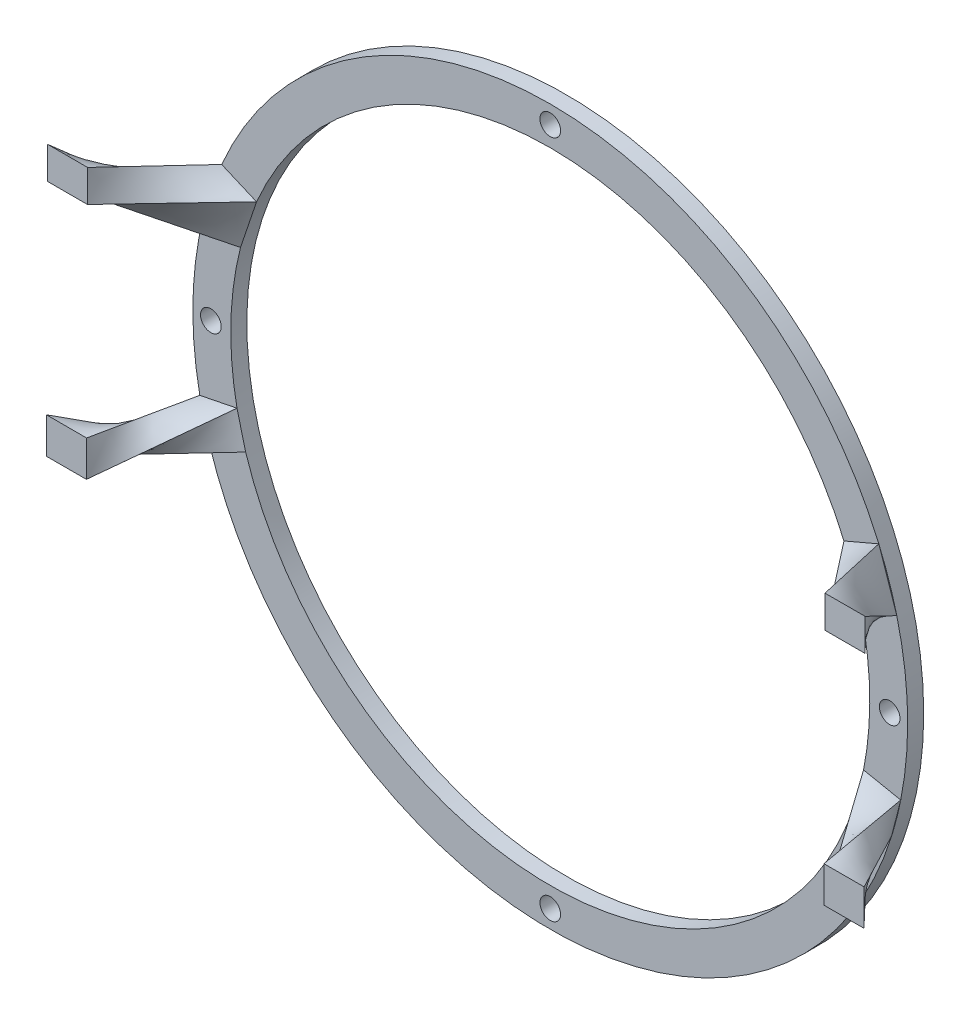
SolidWorks part; units mm, degrees
ref_plane "Front Plane" through (0, 0, 0) normal (0, 0, 1) x (1, 0, 0)
ref_plane "Top Plane" through (0, 0, 0) normal (0, 1, 0) x (1, 0, 0)
ref_plane "Right Plane" through (0, 0, 0) normal (1, 0, 0) x (0, 0, -1)
sketch "Sketch1" plane through (0, 0, 0) normal (0, 0, 1) x (1, 0, 0)
  circle A0 centre (0, 0) radius 89.0365
  circle A1 centre (0, 0) radius 79.5898
  circle A2 centre (0, -84.548) radius 2.5745
  circle A3 centre (-84.548, 0) radius 2.5745
  circle A4 centre (0, 84.548) radius 2.5745
  circle A5 centre (84.548, 0) radius 2.5745
  point P16 (0, 0)
  dimension "D1" = 4
extrude "Boss-Extrude1" add sketch "Sketch1" along normal blind 4
sketch "Sketch2" plane through (0, 0, 4) normal (0, 0, 1) x (1, 0, 0)
  line L2 (86.3259, 21.8023) -> (77.1668, 19.4891)
  line L3 (81.8463, 35.0527) -> (73.1625, 31.3336)
  line L4 (81.8463, 167.6928) -> (81.8463, 27.8766) construction
  line L5 (73.1625, 31.3336) -> (77.1668, 19.4891)
  line L6 (81.8463, 35.0527) -> (86.3259, 21.8023)
  circle A0 centre (0, 0) radius 89.0365 construction
  circle A1 centre (0, 0) radius 79.5898 construction
sketch "Sketch3" plane through (0, 0.1239, 27.5876) normal (0, -0.0045, -1) x (-1, 0, 0)
  line L0 (-101.8463, 40.9901) -> (-101.8463, 33.011)
  line L3 (-91.8463, 40.9901) -> (-91.8463, 33.011)
  line L6 (-101.8463, 40.9901) -> (-91.8463, 40.9901)
  line L7 (-101.8463, -36.3437) -> (-101.8463, 50.7621) construction
  line L8 (-91.8463, -36.3437) -> (-91.8463, 50.7621) construction
  line L9 (-101.8463, 33.011) -> (-91.8463, 33.011)
loft "Loft1" add section "Sketch3" section "Sketch2" connector at (101.8463, 41.1136, 27.4035) connector at (86.3259, 21.8023, 4)
sketch "Sketch8" plane through (0, 0, 4) normal (0, 0, 1) x (1, 0, 0)
  line L3 (78.0403, -15.6285) -> (87.3031, -17.4835)
  line L4 (87.3031, -17.4835) -> (85.0502, -26.3434)
  line L5 (85.0502, -26.3434) -> (75.8813, -24.0119)
  line L6 (75.8813, -24.0119) -> (78.0403, -15.6285)
  arc A3 (73.1625, 31.3336) -> (77.1668, 19.4891) centre (0, 0) ccw construction
  arc A4 (81.8463, 35.0527) -> (86.3259, 21.8023) centre (0, 0) ccw construction
sketch "Sketch9" plane through (0, 0.1239, 27.5876) normal (0, -0.0045, -1) x (-1, 0, 0)
  line L0 (-101.8463, -36.3437) -> (-101.8463, 50.7621) construction
  line L1 (-101.8463, -26.1562) -> (-91.8463, -26.1562)
  line L2 (-91.8463, -36.3437) -> (-91.8463, 50.7621) construction
  line L3 (-91.8463, -26.1562) -> (-91.8463, -17.2417)
  line L4 (-91.8463, -17.2417) -> (-101.8463, -17.2417)
  line L5 (-101.8463, -17.2417) -> (-101.8463, -26.1562)
loft "Loft2" add profiles "Sketch9", "Sketch8" connector at (101.8463, -17.1177, 27.665) connector at (85.0502, -26.3434, 4)
mirror "Mirror1" about plane through (0, 0, 0) normal (1, 0, 0) of "Loft2", "Loft1"
